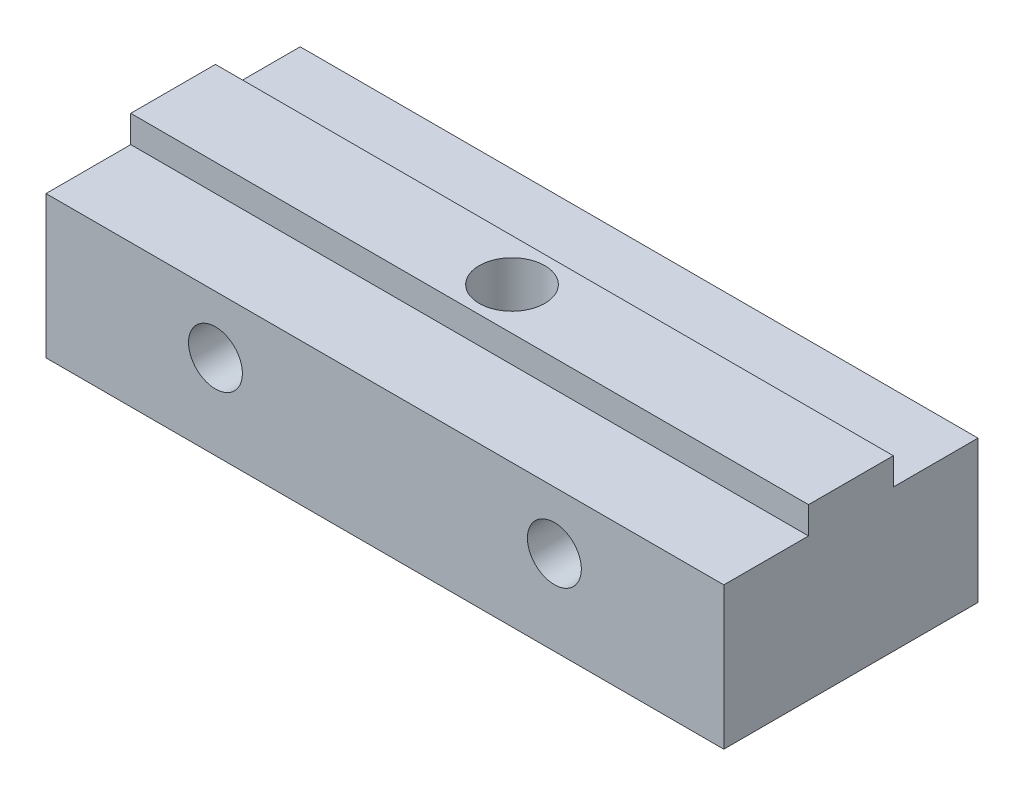
SolidWorks part; units mm, degrees
ref_plane "Front Plane" through (0, 0, 0) normal (0, 0, 1) x (1, 0, 0)
ref_plane "Top Plane" through (0, 0, 0) normal (0, 1, 0) x (1, 0, 0)
ref_plane "Right Plane" through (0, 0, 0) normal (1, 0, 0) x (0, 0, -1)
sketch "Sketch1" plane through (0, 0, 0) normal (0, 1, 0) x (1, 0, 0)
  line L1 (25.4, -9.525) -> (-25.4, -9.525)
  line L2 (25.4, -9.525) -> (25.4, 9.525)
  line L3 (25.4, 9.525) -> (-25.4, 9.525)
  line L4 (-25.4, -9.525) -> (-25.4, 9.525)
  line L5 (25.4, -9.525) -> (-25.4, 9.525) construction
  line L6 (25.4, 9.525) -> (-25.4, -9.525) construction
  point P0 (0, 0)
  dimension "D1" = 50.8
  dimension "D2" = 19.05
extrude "Boss-Extrude1" add sketch "Sketch1" along normal blind 12.7
sketch "Sketch2" plane through (0, 12.7, 0) normal (0, 1, 0) x (1, 0, 0)
  line L0 (-25.4, 9.525) -> (-25.4, -9.525) construction
  line L1 (25.4, -3.175) -> (-25.4, -3.175)
  line L2 (25.4, -3.175) -> (25.4, 3.175)
  line L3 (25.4, 3.175) -> (-25.4, 3.175)
  line L4 (-25.4, -3.175) -> (-25.4, 3.175)
  line L5 (25.4, -3.175) -> (-25.4, 3.175) construction
  line L6 (25.4, 3.175) -> (-25.4, -3.175) construction
  point P0 (0, 0)
  dimension "D1" = 6.35
hole_wizard "#10-32 Tapped Hole1" positions "Sketch3" profile "Sketch4" tap size "#10-32" standard "ANSI Inch" end condition through all
sketch "Sketch3" plane through (0, 0, -9.525) normal (0, 0, -1) x (-1, 0, 0)
  line L0 (-25.4, 6.35) -> (25.4, 6.35) construction
  line L1 (-25.4, 12.7) -> (-25.4, 0) construction
  line L2 (25.4, 12.7) -> (25.4, 0) construction
  point P9 (-12.7, 6.35)
  point P11 (12.7, 6.35)
  dimension "D1" = 12.7
  dimension "D2" = 12.7
sketch "Sketch4" plane through (-12.7, 6.35, -9.525) normal (1, 0, 0) x (0, 1, 0)
  line L0 (0, 0) -> (0, 19.05)
  line L1 (0, 19.05) -> (2.0193, 19.05)
  line L2 (2.0193, 19.05) -> (2.0193, 0)
  line L5 (2.0193, 0) -> (0, 0)
  line L11 (0, -6.35) -> (0, 107.95) construction
  dimension "Thread Major Dia." = 4.0386
  dimension "Thru Tap Drill Depth" = 19.05
hole_wizard "#10 (0.1935) Diameter Hole1" positions "Sketch5" profile "Sketch6" hole size "#10" standard "ANSI Inch" end condition through all
sketch "Sketch5" plane through (0, 0, 0) normal (0, -1, 0) x (-1, 0, 0)
  point P24 (0, 0)
  point P28 (0, 0)
  point P29 (0, 0)
  point P30 (0, 0)
  point P31 (0, 0)
sketch "Sketch6" plane through (0, 0, 0) normal (1, 0, 0) x (0, 0, -1)
  line L0 (0, 0) -> (0, 12.7)
  line L1 (0, 12.7) -> (2.4574, 12.7)
  line L2 (2.4574, 12.7) -> (2.4574, 0)
  line L5 (2.4574, 0) -> (0, 0)
  line L11 (0, -6.35) -> (0, 107.95) construction
  dimension "Thru Hole Dia." = 4.9149
  dimension "Thru Hole Depth" = 12.7
extrude "Cut-Extrude1" cut sketch "Sketch2" against normal blind 2.032 flip side to cut contours L3 L4 L1 L2
